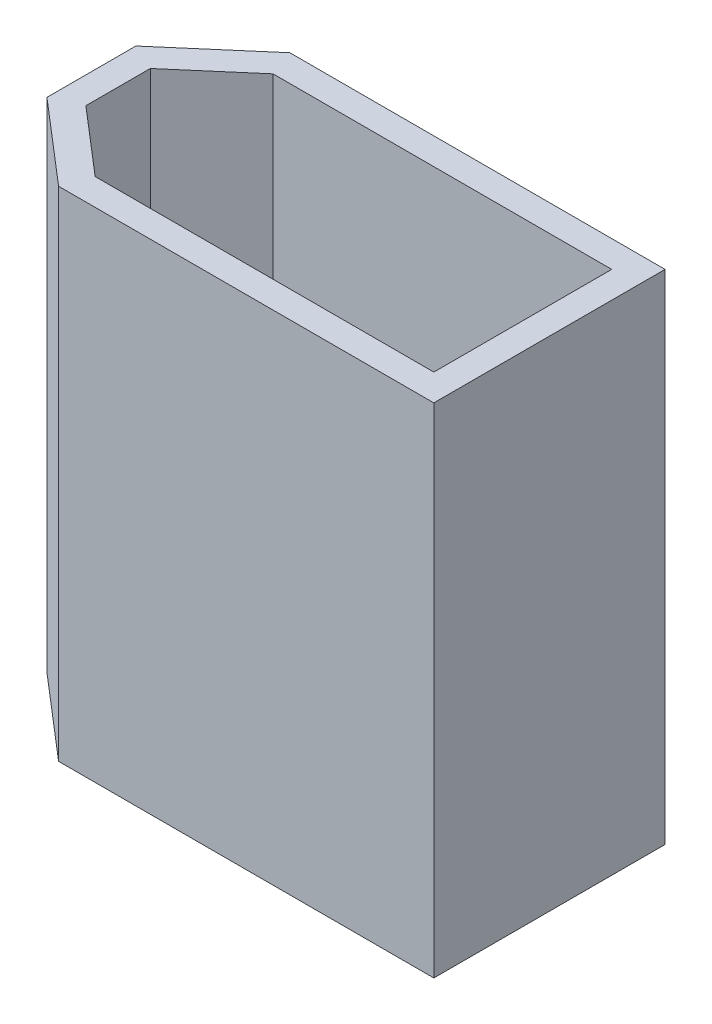
SolidWorks part; units mm, degrees
ref_plane "Front Plane" through (0, 0, 0) normal (0, 0, 1) x (1, 0, 0)
ref_plane "Top Plane" through (0, 0, 0) normal (0, 1, 0) x (1, 0, 0)
ref_plane "Right Plane" through (0, 0, 0) normal (1, 0, 0) x (0, 0, -1)
sketch "Sketch1" plane through (0, 0, 0) normal (0, 1, 0) x (1, 0, 0)
  line L0 (-3.2881, 2.6) -> (-5.15, 1)
  line L1 (5.15, -2.6) -> (-3.2881, -2.6)
  line L2 (5.15, -2.6) -> (5.15, 2.6)
  line L3 (5.15, 2.6) -> (-3.2881, 2.6)
  line L4 (-5.15, -1) -> (-5.15, 1)
  line L5 (5.15, -2.6) -> (-5.15, 2.6) construction
  line L6 (5.15, 2.6) -> (-5.15, -2.6) construction
  line L7 (-3.2881, -2.6) -> (-5.15, -1)
  line L8 (-5.15, 1) -> (-5.15, -1) construction
  line L9 (-3.2881, 2.6) -> (-5.15, 2.6) construction
  line L10 (-5.15, 2.6) -> (-5.15, 1) construction
  line L11 (-3.2881, -2.6) -> (-5.15, -2.6) construction
  line L12 (-5.15, -2.6) -> (-5.15, -1) construction
  line L13 (4.55, 2) -> (-3.0657, 2)
  line L14 (-3.0657, 2) -> (-4.55, 0.7245)
  line L15 (-4.55, -0.7245) -> (-4.55, 0.7245)
  line L16 (-3.0657, -2) -> (-4.55, -0.7245)
  line L17 (4.55, -2) -> (-3.0657, -2)
  line L18 (4.55, -2) -> (4.55, 2)
  point P0 (0, 0)
  point P10 (-5.15, 0)
  point P11 (-3.2881, -2.6)
  dimension "D1" = 10.3
  dimension "D2" = 5.2
  dimension "D3" = 2.455
  dimension "D4" = 2
  dimension "D5" = 0.6
extrude "Boss-Extrude1" add sketch "Sketch1" along normal blind 11.2
